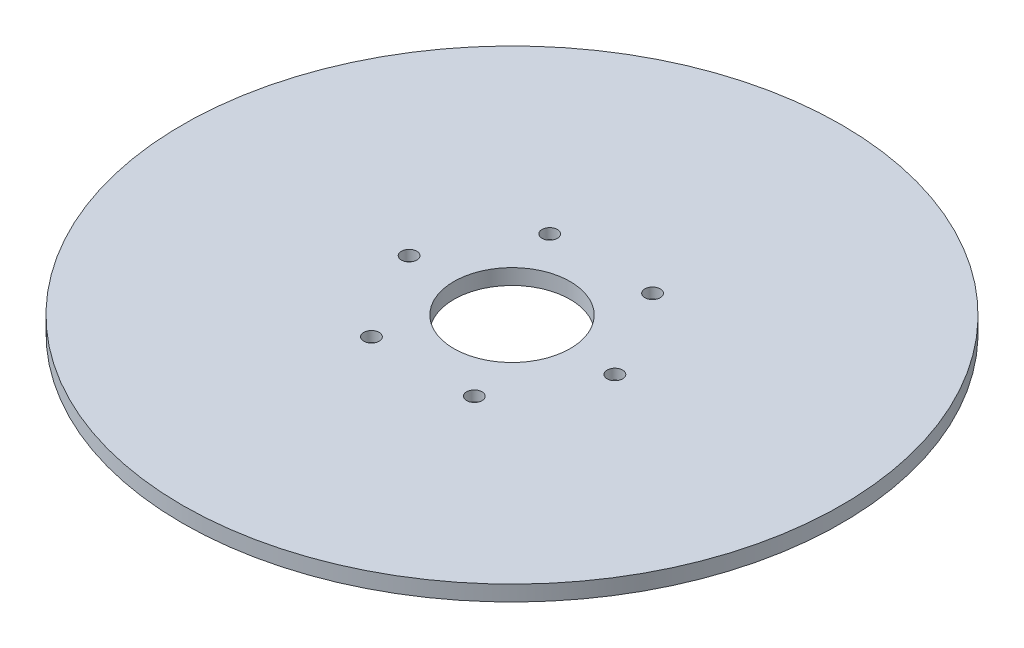
SolidWorks part; units mm, degrees
ref_plane "Front Plane" through (0, 0, 0) normal (0, 0, 1) x (1, 0, 0)
ref_plane "Top Plane" through (0, 0, 0) normal (0, 1, 0) x (1, 0, 0)
ref_plane "Right Plane" through (0, 0, 0) normal (1, 0, 0) x (0, 0, -1)
sketch "Sketch1" plane through (0, 0, 0) normal (0, 1, 0) x (1, 0, 0)
  circle A0 centre (0, 0) radius 85
  dimension "FLANGE_OD" = 170
extrude "Boss-Extrude1" add sketch "Sketch1" along normal blind 4
sketch "Sketch2" plane through (0, 0, 0) normal (0, 1, 0) x (1, 0, 0)
  circle A0 centre (0, 0) radius 15
  dimension "BORE_D" = 30
extrude "Cut-Extrude1" cut sketch "Sketch2" along normal through all
sketch "Sketch3" plane through (0, 4, 0) normal (0, 1, 0) x (1, 0, 0)
  circle A0 centre (0, 0) radius 26.5399 construction
  circle A1 centre (-26.5399, 0) radius 1.9875
  dimension "BOLT_D" = 3.975
  dimension "BOLT_PCD" = 53.0799
extrude "Cut-Extrude2" cut sketch "Sketch3" against normal blind 2.6776
pattern_circular "CirPattern1" count 6 over 360 about axis through (0, 0, 0) along (0, 1, 0) of "Cut-Extrude2"
